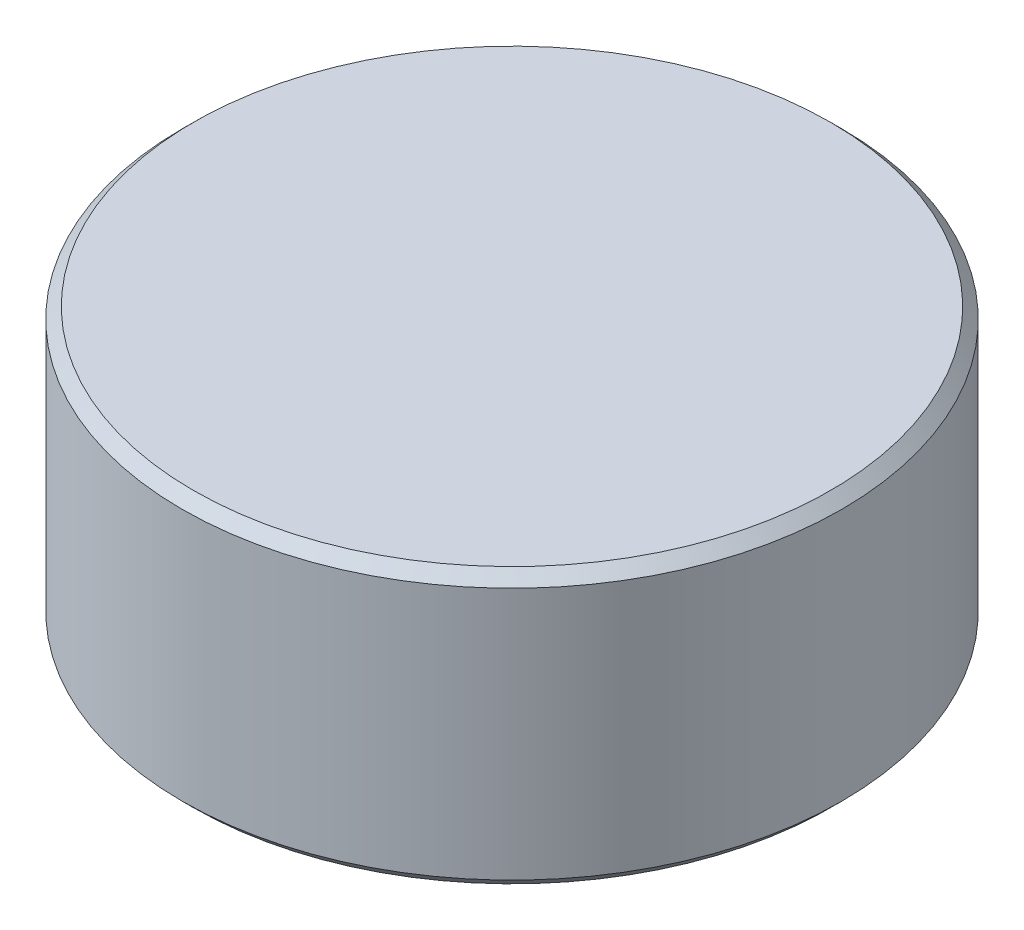
SolidWorks part; units mm, degrees
material "NdFeB"
ref_plane "Front Plane" through (0, 0, 0) normal (0, 0, 1) x (1, 0, 0)
ref_plane "Top Plane" through (0, 0, 0) normal (0, 1, 0) x (1, 0, 0)
ref_plane "Right Plane" through (0, 0, 0) normal (1, 0, 0) x (0, 0, -1)
ref_axis "X Axis" through (88.99, 0, 0) along (-1, 0, 0)
ref_axis "Y Axis" through (0, 55, 0) along (0, -1, 0)
ref_axis "Z Axis" through (0, 0, -88.99) along (0, 0, 1)
sketch "Sketch1" plane through (0, 0, 0) normal (0, 1, 0) x (1, 0, 0)
  circle A0 centre (0, 0) radius 3
  dimension "D1" = 6
extrude "Boss-Extrude1" add sketch "Sketch1" along normal mid plane 2.5
chamfer "Chamfer1" distance 0.1 angle 45 2 edges at (0, -1.25, 3) (0, 1.25, 3)
